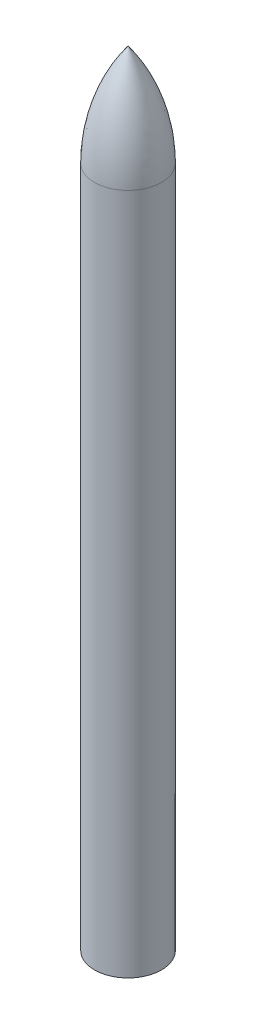
SolidWorks part; units mm, degrees
material "Custom Plastic"
ref_plane "Front Plane" through (0, 0, 0) normal (0, 0, 1) x (1, 0, 0)
ref_plane "Top Plane" through (0, 0, 0) normal (0, 1, 0) x (1, 0, 0)
ref_plane "Right Plane" through (0, 0, 0) normal (1, 0, 0) x (0, 0, -1)
sketch "Sketch3" plane through (0, 0, 0) normal (0, 0, 1) x (1, 0, 0)
  line L0 (0, 0) -> (0, 3209.544) construction
  line L1 (0, 0) -> (-137.16, 0) construction
  line L2 (-137.16, 0) -> (-137.16, 2794)
  line L3 (-133.985, 0) -> (-133.985, 2794)
  line L4 (0, 3209.544) -> (0, 3204.1881)
  line L5 (-137.16, 0) -> (-133.985, 0)
  arc A0 (-137.16, 2794) -> (0, 3209.544) centre (560.8922, 2794) cw
  arc A1 (-133.985, 2794) -> (0, 3204.1881) centre (560.8922, 2794) cw
  arc A2 (-133.985, 2794) -> (2.5511, 3207.654) centre (560.8922, 2794) cw construction
  dimension "D1" = 3209.544
  dimension "D2" = 137.16
  dimension "D3" = 2794
  dimension "D4" = 3.175
revolve "Revolve1" add sketch "Sketch3" angle 360 about L0
